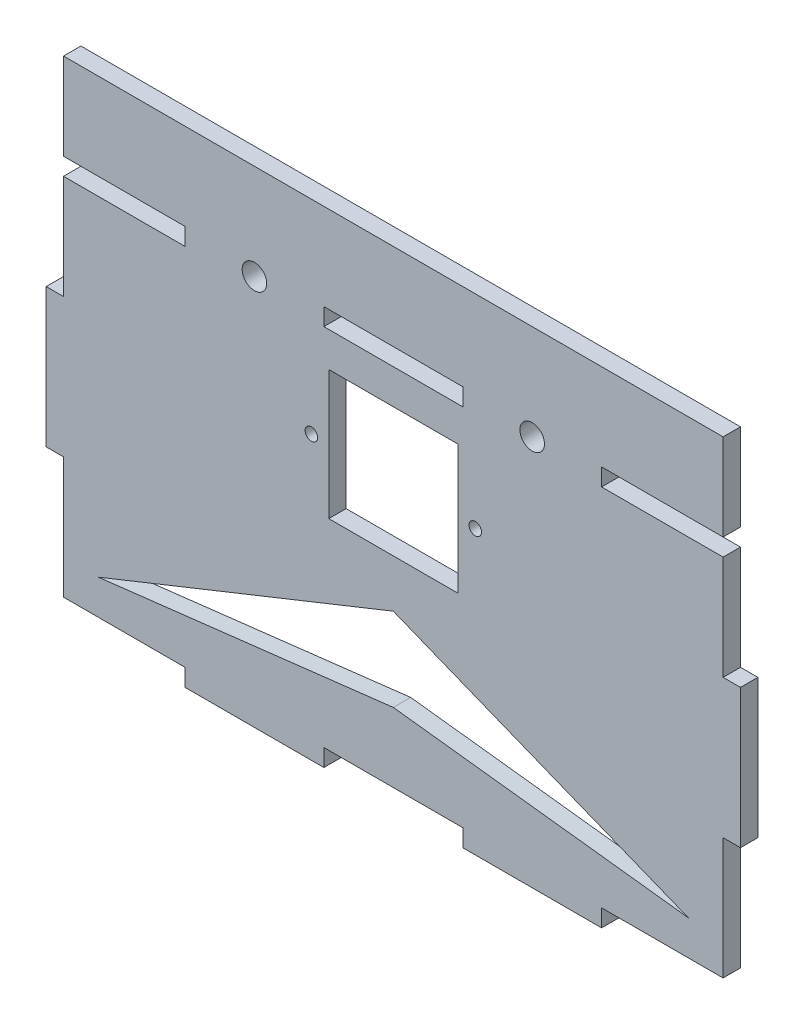
SolidWorks part; units mm, degrees
ref_plane "Front Plane" through (0, 0, 0) normal (0, 0, 1) x (1, 0, 0)
ref_plane "Top Plane" through (0, 0, 0) normal (0, 1, 0) x (1, 0, 0)
ref_plane "Right Plane" through (0, 0, 0) normal (1, 0, 0) x (0, 0, -1)
sketch "Sketch1" plane through (0, 0, 0) normal (0, 0, 1) x (1, 0, 0)
  line L1 (0, 0) -> (127, 0)
  line L2 (0, 0) -> (0, 88.9)
  line L3 (0, 88.9) -> (127, 88.9)
  line L4 (127, 0) -> (127, 88.9)
  dimension "D1" = 127
  dimension "D2" = 88.9
extrude "Boss-Extrude1" add sketch "Sketch1" along normal blind 3.175
sketch "Sketch5" plane through (0, 0, 3.175) normal (0, 0, 1) x (1, 0, 0)
  line L1 (0, 0) -> (3.175, 0)
  line L2 (0, 0) -> (0, 25.4)
  line L3 (0, 25.4) -> (3.175, 25.4)
  line L4 (3.175, 0) -> (3.175, 25.4)
  dimension "D1" = 25.4
  dimension "D2" = 3.175
extrude "Cut-Extrude4" cut sketch "Sketch5" against normal blind 6.35
sketch "Sketch6" plane through (0, 0, 3.175) normal (0, 0, 1) x (1, 0, 0)
  line L1 (0, 0) -> (25.4, 0)
  line L2 (0, 0) -> (0, 3.175)
  line L3 (0, 3.175) -> (25.4, 3.175)
  line L4 (25.4, 0) -> (25.4, 3.175)
  dimension "D1" = 3.175
  dimension "D2" = 25.4
extrude "Cut-Extrude5" cut sketch "Sketch6" against normal blind 6.35
pattern_linear "LPattern5" count 3 spacing 50.8 along (0, 1, 0) count 2 spacing 123.825 along (1, 0, 0) of "Cut-Extrude4"
pattern_linear "LPattern6" count 3 spacing 50.8 along (1, 0, 0) count 2 spacing 69.85 along (0, 1, 0) of "Cut-Extrude5"
hole_wizard "#8 Clearance Hole1" positions "Sketch10" profile "Sketch9" hole size "#8" standard "ANSI Inch"
sketch "Sketch10" plane through (0, 0, 3.175) normal (0, 0, 1) x (1, 0, 0)
  line L2 (25.4, 69.85) -> (25.4, 73.025) construction
  line L3 (76.2, 73.025) -> (50.8, 73.025) construction
  point P0 (38.1, 71.4375)
  point P2 (88.9, 71.4375)
  point P10 (25.4, 71.4375)
  dimension "D1" = 12.7
  dimension "D3" = 12.7
  dimension "D4" = 1.5875
sketch "Sketch9" plane through (38.1, 71.4375, 3.175) normal (1, 0, 0) x (0, -1, 0)
  line L0 (0, 0) -> (0, 11.5107)
  line L1 (0, 11.5107) -> (2.2479, 10.16)
  line L2 (2.2479, 10.16) -> (2.2479, 0)
  line L5 (2.2479, 0) -> (0, 0)
  line L10 (0, 11.5107) -> (-2.2479, 10.16) construction
  line L11 (0, -6.35) -> (0, 107.95) construction
  dimension "Hole Dia." = 4.4958
  dimension "Hole Depth" = 10.16
  dimension "Drill Angle" = 118
sketch "Sketch11" plane through (0, 0, 3.175) normal (0, 0, 1) x (1, 0, 0)
  line L0 (50.8, 69.85) -> (76.2, 69.85) construction
  line L1 (51.689, 39.878) -> (75.311, 39.878)
  line L2 (51.689, 39.878) -> (51.689, 63.5)
  line L3 (51.689, 63.5) -> (75.311, 63.5)
  line L4 (75.311, 39.878) -> (75.311, 63.5)
  line L6 (0, 88.9) -> (0, 76.2) construction
  circle A0 centre (48.514, 51.689) radius 1.143
  circle A1 centre (78.486, 51.689) radius 1.143
  point P6 (63.5, 39.878)
  point P13 (75.311, 51.689)
  point P14 (51.689, 51.689)
  dimension "D5" = 2.286
  dimension "D6" = 2.286
  dimension "D7" = 14.986
  dimension "D8" = 14.986
  dimension "D1" = 6.35
  dimension "D2" = 23.622
  dimension "D3" = 23.622
  dimension "D4" = 63.5
extrude "Cut-Extrude8" cut sketch "Sketch11" against normal blind 7.62
sketch "Sketch14" plane through (0, 0, 0) normal (0, 0, -1) x (-1, 0, 0)
  line L0 (-117.475, 9.525) -> (-63.5, 31.115)
  line L1 (-63.5, 31.115) -> (-9.525, 9.525)
  line L2 (-9.525, 9.525) -> (-63.5, 15.875)
  line L3 (-63.5, 15.875) -> (-117.475, 9.525)
  line L4 (-75.311, 39.878) -> (-51.689, 39.878) construction
  line L5 (-123.825, 25.4) -> (-123.825, 3.175) construction
  line L6 (-123.825, 3.175) -> (-101.6, 3.175) construction
  line L7 (-3.175, 3.175) -> (-3.175, 25.4) construction
  line L8 (-25.4, 3.175) -> (-3.175, 3.175) construction
  line L9 (-76.2, 3.175) -> (-50.8, 3.175) construction
  point P6 (-63.5, 39.878)
  point P15 (-63.5, 3.175)
  dimension "D1" = 15.24
  dimension "D2" = 6.35
  dimension "D3" = 6.35
  dimension "D4" = 6.35
  dimension "D5" = 6.35
  dimension "D6" = 12.7
extrude "Cut-Extrude11" cut sketch "Sketch14" against normal blind 12.7
sketch "Sketch16" plane through (0, 0, 0) normal (0, 0, -1) x (-1, 0, 0)
  line L1 (-127, 88.9) -> (-123.825, 88.9)
  line L2 (-127, 88.9) -> (-127, 76.2)
  line L3 (-127, 76.2) -> (-123.825, 76.2)
  line L4 (-123.825, 88.9) -> (-123.825, 76.2)
  line L5 (0, 88.9) -> (-3.175, 88.9)
  line L6 (0, 88.9) -> (0, 76.2)
  line L7 (0, 76.2) -> (-3.175, 76.2)
  line L8 (-3.175, 88.9) -> (-3.175, 76.2)
extrude "Cut-Extrude13" cut sketch "Sketch16" against normal blind 5.08
